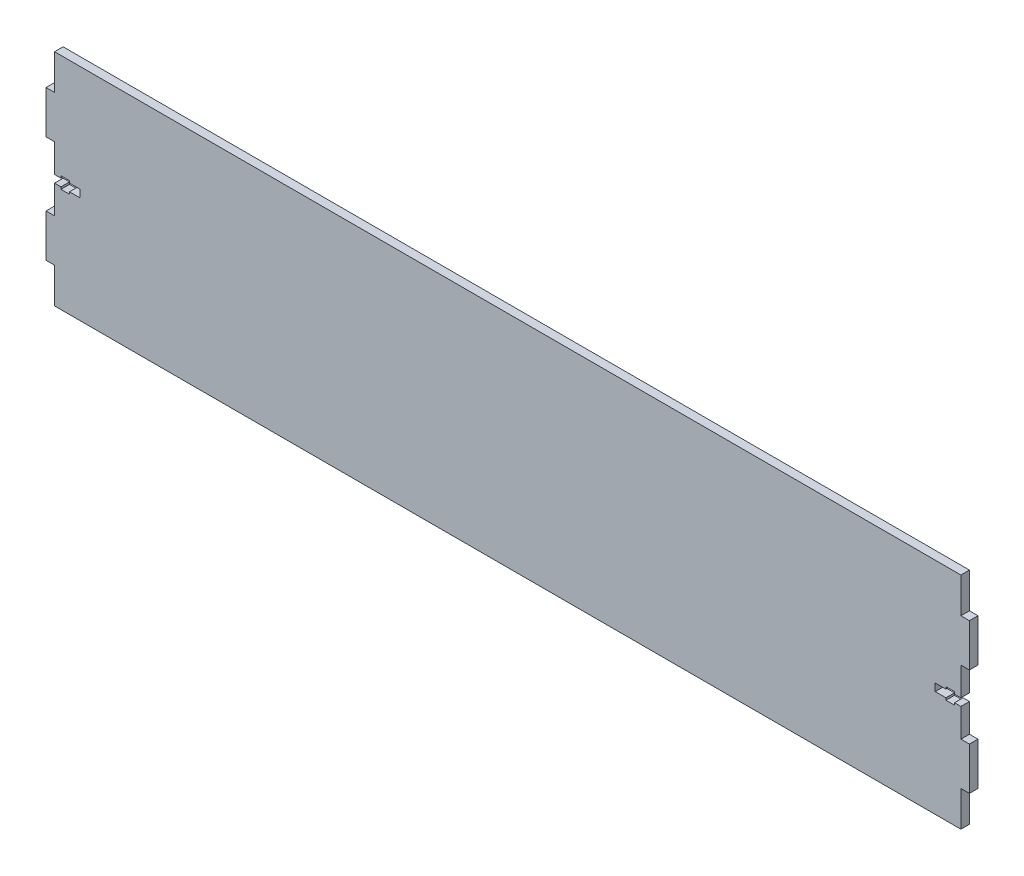
SolidWorks part; units mm, degrees
material "1060 Alloy"
ref_plane "Front Plane" through (0, 0, 0) normal (0, 0, 1) x (1, 0, 0)
ref_plane "Top Plane" through (0, 0, 0) normal (0, 1, 0) x (1, 0, 0)
ref_plane "Right Plane" through (0, 0, 0) normal (1, 0, 0) x (0, 0, -1)
sketch "Sketch1" plane through (0, 0, 0) normal (0, 0, 1) x (1, 0, 0)
  line L0 (212, -51.5) -> (-212, 51.5) construction
  line L1 (-212, 51.5) -> (212, 51.5)
  line L2 (-212, 51.5) -> (-212, -51.5)
  line L3 (-212, -51.5) -> (212, -51.5)
  line L4 (212, 51.5) -> (212, -51.5)
  dimension "D1" = 103
  dimension "D2" = 424
sheet metal parameters "Sheet-Metal1" thickness 4 parameters "D1"=5
base flange "Base-Flange1" sketch "Sketch1" thickness 4 reverse thickness direction no parameters "D1"=5
sketch "Sketch4" plane through (0, 0, 0) normal (0, 0, 1) x (1, 0, 0)
  line L0 (-212, 51.5) -> (-212, -51.5) construction
  line L1 (-212, 35) -> (-216, 35)
  line L2 (-212, 35) -> (-212, 15)
  line L3 (-212, 15) -> (-216, 15)
  line L4 (-216, 35) -> (-216, 15)
  line L5 (212, -51.5) -> (212, 51.5) construction
  line L6 (-212, -15) -> (-216, -15)
  line L7 (-212, -15) -> (-212, -35)
  line L8 (-212, -35) -> (-216, -35)
  line L9 (-216, -15) -> (-216, -35)
  line L10 (212, 35) -> (216, 35)
  line L11 (212, 35) -> (212, 15)
  line L12 (212, 15) -> (216, 15)
  line L13 (216, 35) -> (216, 15)
  line L14 (212, -25) -> (-212, -25) construction
  line L15 (212, -15) -> (216, -15)
  line L16 (212, -15) -> (212, -35)
  line L17 (212, -35) -> (216, -35)
  line L18 (216, -15) -> (216, -35)
  line L19 (-212, 25) -> (212, 25) construction
  line L20 (0, 25) -> (0, -25) construction
  dimension "D1" = 4
  dimension "D2" = 20
  dimension "D3" = 50
base flange "Tab1" sketch "Sketch4" thickness 4 reverse thickness direction no parameters "D1"=5
sketch "Sketch5" plane through (0, 0, 0) normal (0, 0, 1) x (1, 0, 0)
  line L0 (-212, 1.75) -> (-209, 1.75)
  line L1 (-212, 51.5) -> (-212, -51.5) construction
  line L2 (-209, 1.75) -> (-209, 2.75)
  line L3 (-209, 2.75) -> (-205, 2.75)
  line L4 (-205, 2.75) -> (-205, 1.75)
  line L5 (-205, 1.75) -> (-200, 1.75)
  line L6 (-200, 1.75) -> (-200, -1.75)
  line L7 (-200, -1.75) -> (-205, -1.75)
  line L8 (-205, -1.75) -> (-205, -2.75)
  line L9 (-205, -2.75) -> (-209, -2.75)
  line L10 (-209, -2.75) -> (-209, -1.75)
  line L11 (-209, -1.75) -> (-212, -1.75)
  line L12 (-212, 15) -> (-212, -15) construction
  line L13 (-212, -1.75) -> (-212, 1.75)
  line L14 (0, 0) -> (0, -51.5) construction
  line L15 (-212, -51.5) -> (212, -51.5) construction
  line L16 (-212, 0) -> (212, 0) construction
  line L17 (212, -1.75) -> (212, 1.75)
  line L18 (209, -1.75) -> (212, -1.75)
  line L19 (209, -2.75) -> (209, -1.75)
  line L20 (205, -2.75) -> (209, -2.75)
  line L21 (205, -1.75) -> (205, -2.75)
  line L22 (200, -1.75) -> (205, -1.75)
  line L23 (200, 1.75) -> (200, -1.75)
  line L24 (205, 1.75) -> (200, 1.75)
  line L25 (205, 2.75) -> (205, 1.75)
  line L26 (209, 2.75) -> (205, 2.75)
  line L27 (209, 1.75) -> (209, 2.75)
  line L28 (212, 1.75) -> (209, 1.75)
  dimension "D1" = 3.5
  dimension "D2" = 4
  dimension "D3" = 5
  dimension "D4" = 5.5
  dimension "D5" = 3
extrude "Cut-Extrude1" cut sketch "Sketch5" against normal through all normal cut yes
sketch "Sketch6" plane through (0, 0, 0) normal (0, 0, 1) x (1, 0, 0)
  line L0 (-212, -51.5) -> (212, -51.5) construction
  line L1 (-137, -51.5) -> (-88, -51.5)
  line L2 (-137, -51.5) -> (-137, -55.5)
  line L3 (-137, -55.5) -> (-88, -55.5)
  line L4 (-88, -51.5) -> (-88, -55.5)
  line L5 (-212, -51.5) -> (212, -51.5) construction
  line L6 (88, -51.5) -> (137, -51.5)
  line L7 (88, -51.5) -> (88, -55.5)
  line L8 (88, -55.5) -> (137, -55.5)
  line L9 (137, -51.5) -> (137, -55.5)
  line L10 (-88, -55.5) -> (88, -55.5) construction
  line L11 (0, -55.5) -> (0, 0) construction
  line L12 (-112.5, -55.5) -> (-112.5, -51.5) construction
  line L13 (112.5, -55.5) -> (112.5, -51.5) construction
  dimension "D1" = 4
  dimension "D2" = 49
  dimension "D3" = 225
sketch "Sketch7" plane through (0, 0, 0) normal (0, 0, 1) x (1, 0, 0)
  line L0 (-1.75, -51.5) -> (-1.75, -48.5)
  line L1 (-212, -51.5) -> (212, -51.5) construction
  line L2 (-1.75, -48.5) -> (-2.75, -48.5)
  line L3 (-2.75, -48.5) -> (-2.75, -44.5)
  line L4 (-2.75, -44.5) -> (-1.75, -44.5)
  line L5 (-1.75, -44.5) -> (-1.75, -39.5)
  line L6 (-1.75, -39.5) -> (1.75, -39.5)
  line L7 (1.75, -39.5) -> (1.75, -44.5)
  line L8 (1.75, -44.5) -> (2.75, -44.5)
  line L9 (2.75, -44.5) -> (2.75, -48.5)
  line L10 (2.75, -48.5) -> (1.75, -48.5)
  line L11 (1.75, -48.5) -> (1.75, -51.5)
  line L12 (-212, -51.5) -> (212, -51.5) construction
  line L13 (1.75, -51.5) -> (-1.75, -51.5)
  line L14 (0, -51.5) -> (0, 0) construction
  dimension "D1" = 3.5
  dimension "D2" = 5.5
  dimension "D3" = 3
  dimension "D4" = 4
  dimension "D5" = 5
flat pattern "Flat-Pattern1" [suppressed]
sketch "Bend-Lines1" plane through (0, 0, 0) normal (0, 1, 0) x (1, 0, 0)
sketch3d "Bounding-Box1" [suppressed]
  line L0 (-216, -51.5, 0) -> (216, -51.5, 0) construction
  line L1 (-216, 51.5, 0) -> (216, 51.5, 0) construction
  line L2 (-216, -51.5, 0) -> (-216, 51.5, 0) construction
  line L3 (216, -51.5, 0) -> (216, 51.5, 0) construction
